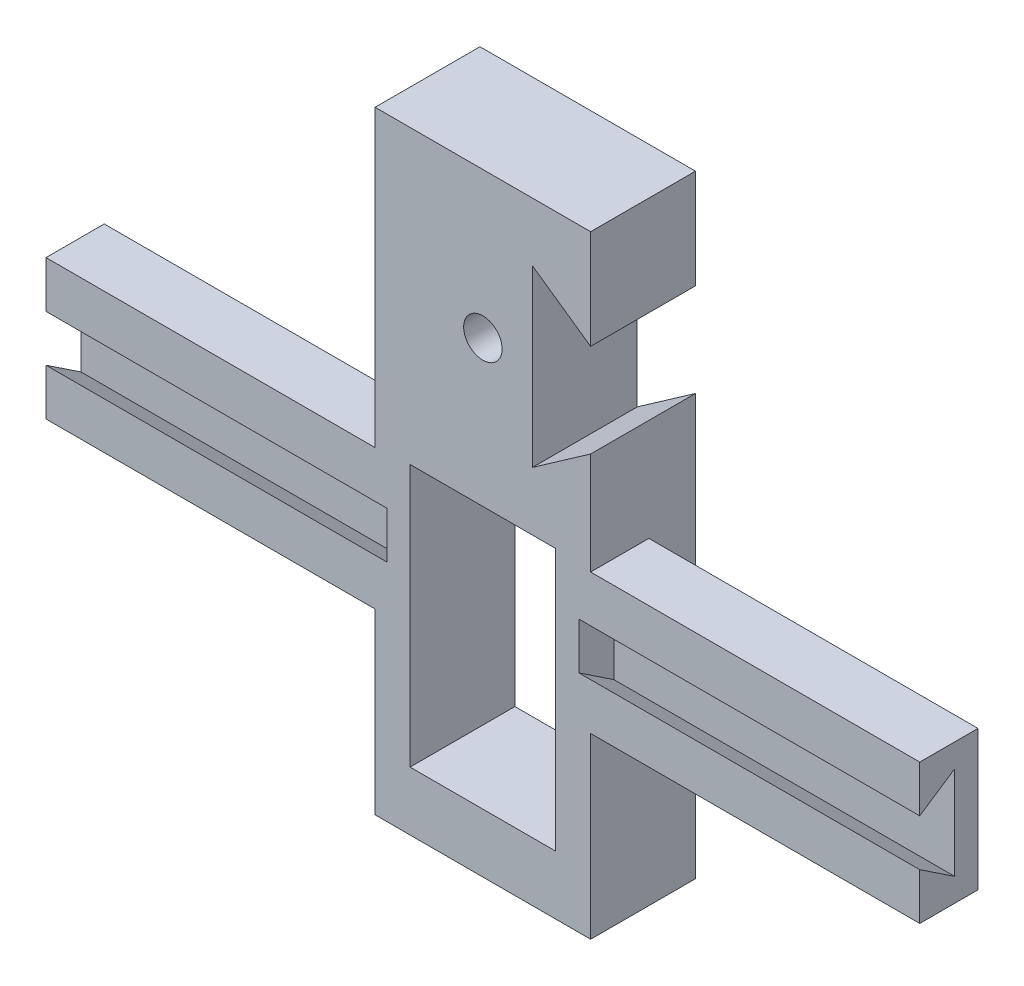
SolidWorks part; units mm, degrees
ref_plane "前视基准面" through (0, 0, 0) normal (0, 0, 1) x (1, 0, 0)
ref_plane "上视基准面" through (0, 0, 0) normal (0, 1, 0) x (1, 0, 0)
ref_plane "右视基准面" through (0, 0, 0) normal (1, 0, 0) x (0, 0, -1)
sketch "草图1" plane through (0, 0, 0) normal (0, 0, 1) x (1, 0, 0)
  line L0 (0, -995.5) -> (0, 49004.5) construction
  line L1 (-6.25, -11.25) -> (6.25, -11.25)
  line L2 (-6.25, -11.25) -> (-6.25, 11.25)
  line L3 (-6.25, 11.25) -> (6.25, 11.25)
  line L4 (6.25, -11.25) -> (6.25, 11.25)
  line L5 (-6.25, -11.25) -> (6.25, 11.25) construction
  line L6 (-6.25, 11.25) -> (6.25, -11.25) construction
  line L11 (0, 0) -> (-19.3596, 0) construction
  line L16 (-9.25, -16.3) -> (9.25, -16.3)
  line L17 (-9.25, -16.3) -> (-9.25, 16.3)
  line L18 (-9.25, 16.3) -> (9.25, 16.3)
  line L19 (9.25, -16.3) -> (9.25, 16.3)
  line L20 (-9.25, -16.3) -> (9.25, 16.3) construction
  line L21 (-9.25, 16.3) -> (9.25, -16.3) construction
  line L24 (-37.5, 3.5) -> (37.5, 3.5)
  line L25 (-37.5, 3.5) -> (-37.5, 6.5)
  line L26 (-37.5, 6.5) -> (37.5, 6.5)
  line L27 (37.5, 3.5) -> (37.5, 6.5)
  line L28 (-37.5, 3.5) -> (37.5, 6.5) construction
  line L29 (-37.5, 6.5) -> (37.5, 3.5) construction
  line L31 (-37.5, -1) -> (37.5, -1)
  line L32 (-37.5, -1) -> (-37.5, 11)
  line L33 (-37.5, 11) -> (37.5, 11)
  line L34 (37.5, -1) -> (37.5, 11)
  line L35 (-37.5, -1) -> (37.5, 11) construction
  line L36 (-37.5, 11) -> (37.5, -1) construction
  line L37 (-9.25, 16.3) -> (9.25, 16.3)
  line L38 (-9.25, 16.3) -> (-9.25, 36.3)
  line L39 (-9.25, 36.3) -> (9.25, 36.3)
  line L40 (9.25, 16.3) -> (9.25, 36.3)
  circle A1 centre (0, 5) radius 6.25
  circle A2 centre (0, 5) radius 2.5
  circle A3 centre (0, 13.8) radius 1.5
  circle A4 centre (0, -13.8) radius 1.5
  point P0 (0, 0)
  point P9 (0, 0)
  point P13 (0, -1.25)
  dimension "D1" = 12.5
  dimension "D4" = 5
  dimension "D5" = 3
  dimension "D7" = 3
  dimension "D8" = 2.5
  dimension "D2" = 12.5
  dimension "D3" = 22.5
  dimension "D6" = 5.05
  dimension "D9" = 3
  dimension "D10" = 75
  dimension "D11" = 12
  dimension "D12" = 20
extrude "凸台-拉伸1" add sketch "草图1" along normal blind 5 contours L31 L17 L16 L19 L4 L1 L2 A4 | L33 L4 L26 L19 | L26 L4 L24 L19 | L4 L31 L19 L24 | L33 L17 L26 L2 | L26 L17 L24 L2 | L17 L31 L2 L24 | L26 L34 L33 L19 | L24 L27 L26 L19 | L31 L34 L24 L19 | L32 L31 L17 L24 | L26 L25 L24 L17 | L33 L32 L26 L17 | L17 L33 L2 L3 L4 L19 L18 A3 | A3 | A4 region at (0, -11.4901, 0) region at (-7.75, 1.25, 0) region at (7.75, 1.25, 0) region at (-7.75, 5, 0) region at (-23.375, 1.25, 0) region at (7.75, 5, 0) region at (23.375, 1.25, 0) region at (-23.375, 5, 0) region at (23.375, 5, 0) region at (-7.75, 8.75, 0) region at (-23.375, 8.75, 0) region at (7.75, 8.75, 0) region at (23.375, 8.75, 0) region at (-7.75, 11.1924, 0) region at (0, 13.8, 0) region at (0, -13.8, 0)
sketch "草图2" plane through (-37.5, 0, 0) normal (-1, 0, 0) x (0, 0, 1)
  line L1 (5, 5) -> (-5.1602, 5) construction
  line L2 (5, -1) -> (5, 11) construction
  line L3 (5, 7) -> (5, 3)
  line L7 (2, 9) -> (2, 1)
  line L8 (2, 9) -> (5, 7)
  line L9 (5, 3) -> (2, 1)
  point P10 (5, 5)
  point P11 (2, 5)
  dimension "D1" = 4
  dimension "D2" = 8
  dimension "D3" = 3
extrude "切除-拉伸2" cut sketch "草图2" along direction (-1, 0, 0) on the side against the normal offset from surface (29.25 mm away) 2 up to face at (-6.25, 0, 2.5)
sketch "草图3" plane through (37.5, 0, 0) normal (1, 0, 0) x (0, 0, -1)
  line L0 (-5, 5) -> (2.6648, 5) construction
  line L1 (-5, -1) -> (-5, 11) construction
  line L2 (-5, 7) -> (-5, 3)
  line L3 (-2, 9) -> (-2, 1)
  line L4 (-2, 9) -> (-5, 7)
  line L5 (-5, 3) -> (-2, 1)
  point P6 (-5, 5)
  point P9 (-2, 5)
  dimension "D1" = 4
  dimension "D2" = 8
  dimension "D3" = 3
extrude "切除-拉伸4" cut sketch "草图3" against normal offset from surface (29.25 mm away) 2 up to face at (6.25, 0, 2.5)
extrude "凸台-拉伸2" add sketch "草图1<9>" against normal blind 4 contours L17 L33 L2 L3 L4 L19 L18 A3 | L33 L17 L26 L2 | L33 L4 L26 L19 | L26 L4 L24 L19 | L4 L31 L19 L24 | L31 L17 L16 L19 L4 L1 L2 A4 | L17 L31 L2 L24 | L26 L17 L24 L2 region at (0, -11.4901, 0) region at (-7.75, 1.25, 0) region at (7.75, 1.25, 0) region at (-7.75, 5, 0) region at (7.75, 5, 0) region at (-7.75, 8.75, 0) region at (7.75, 8.75, 0) region at (-7.75, 11.1924, 0)
sketch "草图1<9>" plane through (0, 0, 0) normal (0, 0, 1) x (1, 0, 0) same geometry as "草图1"
extrude "凸台-拉伸7" add sketch "草图1<11>" along normal blind 5 and the other way blind 4 contours L18 L40 L39 L38 region at (0, 26.3, 0)
sketch "草图1<11>" plane through (0, 0, 0) normal (0, 0, 1) x (1, 0, 0) same geometry as "草图1"
sketch "草图6" plane through (0, 0, 5) normal (0, 0, 1) x (1, 0, 0)
  line L0 (9.25, 27.775) -> (9.25, 19.775)
  line L1 (-9.25, 23.775) -> (9.25, 23.775) construction
  line L2 (-9.25, -16.3) -> (-9.25, 36.3) construction
  line L3 (9.25, -16.3) -> (9.25, 36.3) construction
  line L4 (-9.25, 36.3) -> (9.25, 36.3) construction
  line L5 (-6.25, 11.25) -> (6.25, 11.25) construction
  line L6 (4.25, 31.275) -> (4.25, 16.275)
  line L7 (4.25, 31.275) -> (9.25, 27.775)
  line L8 (4.25, 16.275) -> (9.25, 19.775)
  circle A0 centre (0, 23.775) radius 1.65
  point P12 (9.25, 23.775)
  point P15 (4.25, 23.775)
  line M11 (9.25, 11) -> (9.25, 36.3)
  dimension "D4" = 3.3
  dimension "D1" = 8
  dimension "D2" = 15
  dimension "D3" = 5
extrude "切除-拉伸5" cut sketch "草图6" against normal through all contours L6 L1 L0 L7 | L1 L6 L8 M11 region at (6.4964, 26.7388, 5) region at (6.4964, 20.8112, 5)
extrude "切除-拉伸7" cut sketch "草图6<4>" along normal up to next from surface contours A0 L1 | L1 A0 region at (0, 23.0747, 5) region at (0, 24.4753, 5) starting at face at (1.5, -13.8, -4)
sketch "草图6<4>" plane through (0, 0, 5) normal (0, 0, 1) x (1, 0, 0) same geometry as "草图6"
sketch "草图9" plane through (-9.25, 0, 0) normal (-1, 0, 0) x (0, 0, 1)
  line L0 (-4, 36.3) -> (5, 36.3) construction
  line L3 (-4, -16.3) -> (-4, 36.3) construction
  line L4 (5, 11) -> (5, 36.3) construction
  line L5 (-4, 23.77) -> (5, 23.77)
  circle A0 centre (0.5, 23.77) radius 1.65
  point P11 (0.5, 23.77)
  dimension "D1" = 12.53
  dimension "D2" = 3.3
extrude "切除-拉伸8" cut sketch "草图9" against normal blind 11 contours L5 A0 | L5 A0 region at (-9.25, 24.4703, 0.5) region at (-9.25, 23.0697, 0.5)
sketch "草图10" plane through (0, 0, 0) normal (0, 0, -1) x (-1, 0, 0)
  circle A0 centre (0, 13.8) radius 1.5
  circle A1 centre (0, -13.8) radius 1.5
extrude "切除-拉伸9" cut sketch "草图10" against normal blind 2
